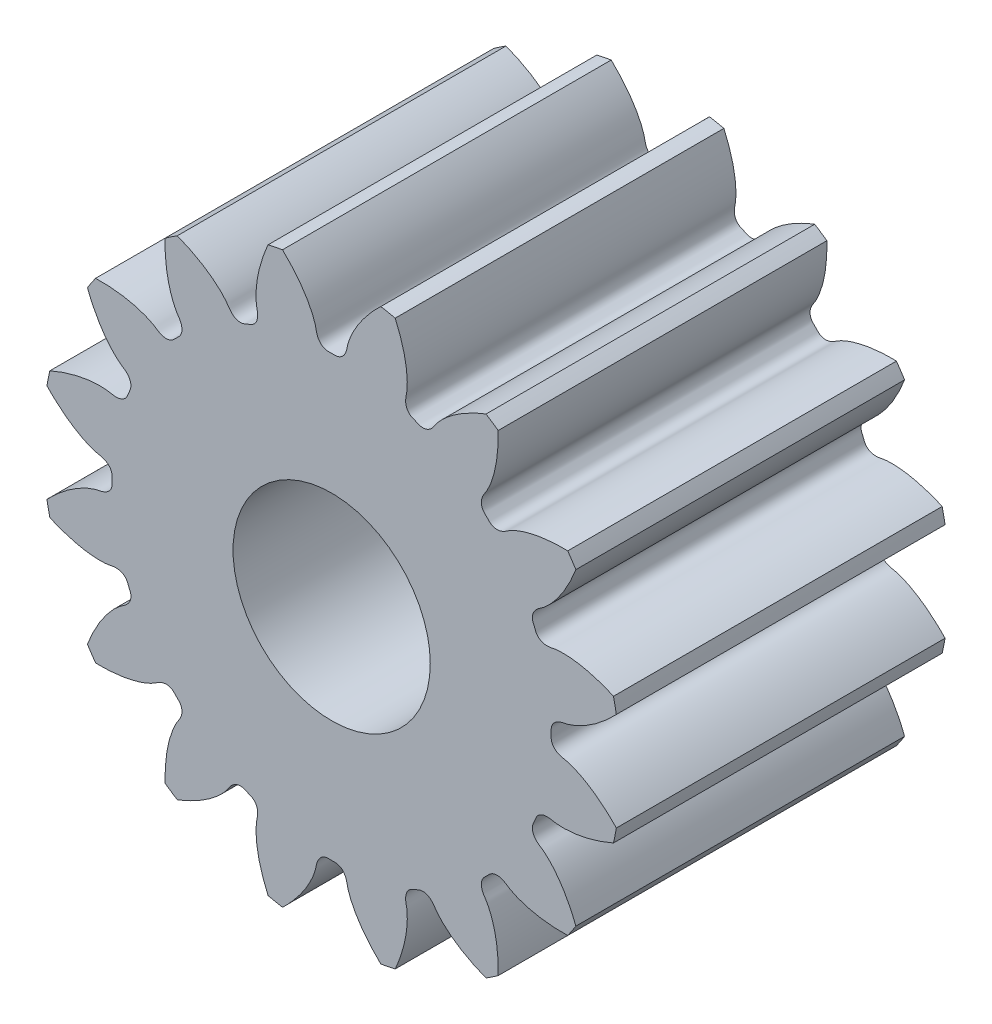
SolidWorks part; units mm, degrees
material "Д16 ГОСТ 4784-97"
ref_plane "FRONT" through (0, 0, 0) normal (0, 0, 1) x (1, 0, 0)
ref_plane "TOP" through (0, 0, 0) normal (0, 1, 0) x (1, 0, 0)
ref_plane "RIGHT" through (0, 0, 0) normal (1, 0, 0) x (0, 0, -1)
ref_axis "Ось1" through (0, 0, 50) along (0, 0, -1)
sketch "SketchRevolveSpurAssemblyNew1Pinion" plane through (0, 0, 0) normal (1, 0, 0) x (0, 0, -1)
  line L0 (0, 0) -> (1, 0) construction
  line L1 (-4, 0) -> (-4, 8.7891)
  line L2 (-4, 8.7891) -> (6, 8.7891)
  line L3 (6, 8.7891) -> (6, 0)
  line L4 (6, 0) -> (-4, 0)
  dimension "D1" = 4
  dimension "D2" = 10
revolve "SpurAssemblyNew1Pinion" add sketch "SketchRevolveSpurAssemblyNew1Pinion" angle 360 about L0
sketch "SketchToothSpurAssemblyNew1Pinion" plane through (0, 0, 0) normal (0, 0, 1) x (1, 0, 0)
  arc A0 (8.716, 1.5542) -> (8.716, -1.5542) centre (0, 0) cw
  spline S0 degree 3 poles (8.716, -1.5542) (8.6286, -1.4593) (8.496, -1.3253) (8.3141, -1.1618) (8.1849, -1.0543) (8.0598, -0.958) (7.9394, -0.8724) (7.8244, -0.797) (7.7153, -0.7313) (7.6127, -0.6747) (7.5171, -0.6266) (7.4291, -0.5864) (7.349, -0.5534) (7.2773, -0.5271) (7.2144, -0.5065) (7.1604, -0.4913) (7.098, -0.4758) (7.0463, -0.4679) (7.0043, -0.4578) (6.9857, -0.4529) (6.9673, -0.4474) (6.9491, -0.4414) (6.9309, -0.4347) (6.9128, -0.4273) (6.8947, -0.4192) (6.8765, -0.4101) (6.8582, -0.3999) (6.8397, -0.3884) (6.821, -0.3754) (6.8021, -0.3606) (6.7831, -0.3437) (6.7641, -0.3241) (6.7455, -0.3015) (6.7276, -0.2756) (6.7111, -0.246) (6.697, -0.2126) (6.6863, -0.1759) (6.68, -0.1381) (6.6779, -0.0791) (6.681, 0) (6.6779, 0.0791) (6.68, 0.1381) (6.6863, 0.1759) (6.697, 0.2126) (6.7111, 0.246) (6.7276, 0.2756) (6.7455, 0.3015) (6.7641, 0.3241) (6.7831, 0.3437) (6.8021, 0.3606) (6.821, 0.3754) (6.8397, 0.3884) (6.8582, 0.3999) (6.8765, 0.4101) (6.8947, 0.4192) (6.9128, 0.4273) (6.9309, 0.4347) (6.9491, 0.4414) (6.9673, 0.4474) (6.9857, 0.4529) (7.0043, 0.4578) (7.0463, 0.4679) (7.098, 0.4758) (7.1604, 0.4913) (7.2144, 0.5065) (7.2773, 0.5271) (7.349, 0.5534) (7.4291, 0.5864) (7.5171, 0.6266) (7.6127, 0.6747) (7.7153, 0.7313) (7.8244, 0.797) (7.9394, 0.8724) (8.0598, 0.958) (8.1849, 1.0543) (8.3141, 1.1618) (8.496, 1.3253) (8.6286, 1.4593) (8.716, 1.5542) knots 0 0 0 0 0.07194 0.10507 0.136308 0.165652 0.193102 0.21866 0.242325 0.264096 0.283974 0.301959 0.318051 0.33225 0.344555 0.354968 0.363487 0.380444 0.384031 0.387599 0.39116 0.394727 0.398315 0.401941 0.405627 0.409398 0.413281 0.41731 0.421523 0.425965 0.430682 0.435726 0.441147 0.446987 0.453273 0.460003 0.467133 0.474573 0.481319 0.5 0.518681 0.525427 0.532867 0.539997 0.546727 0.553013 0.558853 0.564274 0.569318 0.574035 0.578477 0.58269 0.586719 0.590602 0.594373 0.598059 0.601685 0.605273 0.60884 0.612401 0.615969 0.619556 0.636513 0.645032 0.655445 0.66775 0.681949 0.698041 0.716026 0.735904 0.757675 0.78134 0.806898 0.834348 0.863692 0.89493 0.92806 1 1 1 1
extrude "ToothExtrudeCutSpurAssemblyNew1Pinion" cut sketch "SketchToothSpurAssemblyNew1Pinion" against normal blind 8 and the other way blind 4
pattern_circular "PatternSpurAssemblyNew1Pinion" count 16 every 22.5 about axis through (0, 0, 50) along (0, 0, -1) of "ToothExtrudeCutSpurAssemblyNew1Pinion"
sketch "AuxiliarySketchSpurAssemblyNew1Pinion" plane through (0, 0, 0) normal (0, 0, 1) x (1, 0, 0)
  circle A0 centre (0, 0) radius 7.5 construction
  circle A1 centre (0, 0) radius 7.0477 construction
  circle A2 centre (0, 0) radius 7.0831 construction
  circle A3 centre (0, 0) radius 8.7891 construction
  circle A4 centre (0, 0) radius 6.6797 construction
  dimension "PitchDiameter" = 15
  dimension "BaseDiameter" = 14.0954
  dimension "FormDiameter" = 14.1663
  dimension "MajorDiameter" = 17.5781
  dimension "MinorDiameter" = 13.3594
sketch "Эскиз1" plane through (0, 0, 4) normal (0, 0, 1) x (1, 0, 0)
  circle A0 centre (0, 0) radius 3
  dimension "D1" = 6
extrude "Вырез-Вытянуть1" cut sketch "Эскиз1" against normal through all
